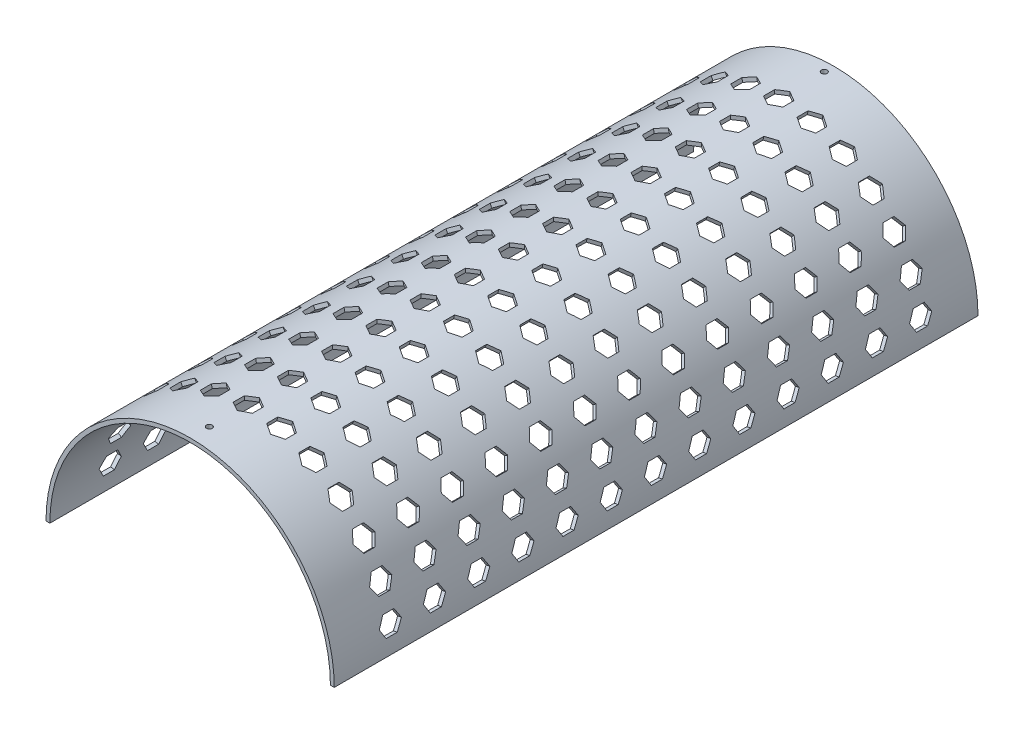
SolidWorks part; units mm, degrees
material "PET"
ref_plane "Front Plane" through (0, 0, 0) normal (0, 0, 1) x (1, 0, 0)
ref_plane "Top Plane" through (0, 0, 0) normal (0, 1, 0) x (1, 0, 0)
ref_plane "Right Plane" through (0, 0, 0) normal (1, 0, 0) x (0, 0, -1)
sketch "Sketch1" plane through (0, 0, 0) normal (0, 0, 1) x (1, 0, 0)
  line L0 (-75, 0) -> (-73, 0)
  line L1 (-73, 0) -> (73, 0) construction
  line L2 (73, 0) -> (75, 0)
  arc A0 (75, 0) -> (-75, 0) centre (0, 0) ccw
  arc A1 (73, 0) -> (-73, 0) centre (0, 0) ccw
  arc A2 (-75, 0) -> (75, 0) centre (0, 0) ccw construction
  circle A3 centre (0, 0) radius 75 construction
  arc A4 (-73, 0) -> (73, 0) centre (0, 0) ccw construction
  circle A5 centre (0, 0) radius 73 construction
  dimension "D1" = 150
  dimension "D2" = 2
extrude "Boss-Extrude1" add sketch "Sketch1" along normal blind 335
sketch "Sketch4" plane through (0, 0, 0) normal (0, 1, 0) x (1, 0, 0)
  line L0 (-75, -335) -> (75, -335) construction
  line L1 (75, 0) -> (-75, 0) construction
  circle A0 centre (0, -5) radius 1.5
  circle A1 centre (0, -325) radius 1.5
  dimension "D1" = 3
  dimension "D3" = 3
  dimension "D2" = 10
  dimension "D4" = 5
extrude "Cut-Extrude2" cut sketch "Sketch4" along normal up to surface (75 mm away) up to face at (0, 37.5, 167.5)
sketch "Sketch2" plane through (0, 0, 0) normal (0, 1, 0) x (1, 0, 0)
  line L0 (0, 0) -> (0, -28.6927) construction
  line L1 (5, -31.5794) -> (5, -25.8059)
  line L2 (5, -25.8059) -> (0, -22.9192)
  line L3 (0, -22.9192) -> (-5, -25.8059)
  line L4 (-5, -25.8059) -> (-5, -31.5794)
  line L5 (-5, -31.5794) -> (0, -34.4662)
  line L6 (0, -34.4662) -> (5, -31.5794)
  circle A1 centre (0, -28.6927) radius 5 construction
  dimension "D1" = 10
extrude "Cut-Extrude3" cut sketch "Sketch2" along normal up to surface (74.8331 mm away) up to face at (0, 37.5, 167.5)
pattern_circular "CirPattern1" count 7 every 13.333 about axis through (0, 0, 335) along (0, 0, -1) of "Cut-Extrude3" reverse direction yes other way count 7
pattern_linear "LPattern1" count 13 spacing 23 along (0, 0, 1) of "CirPattern1", "Cut-Extrude3"
